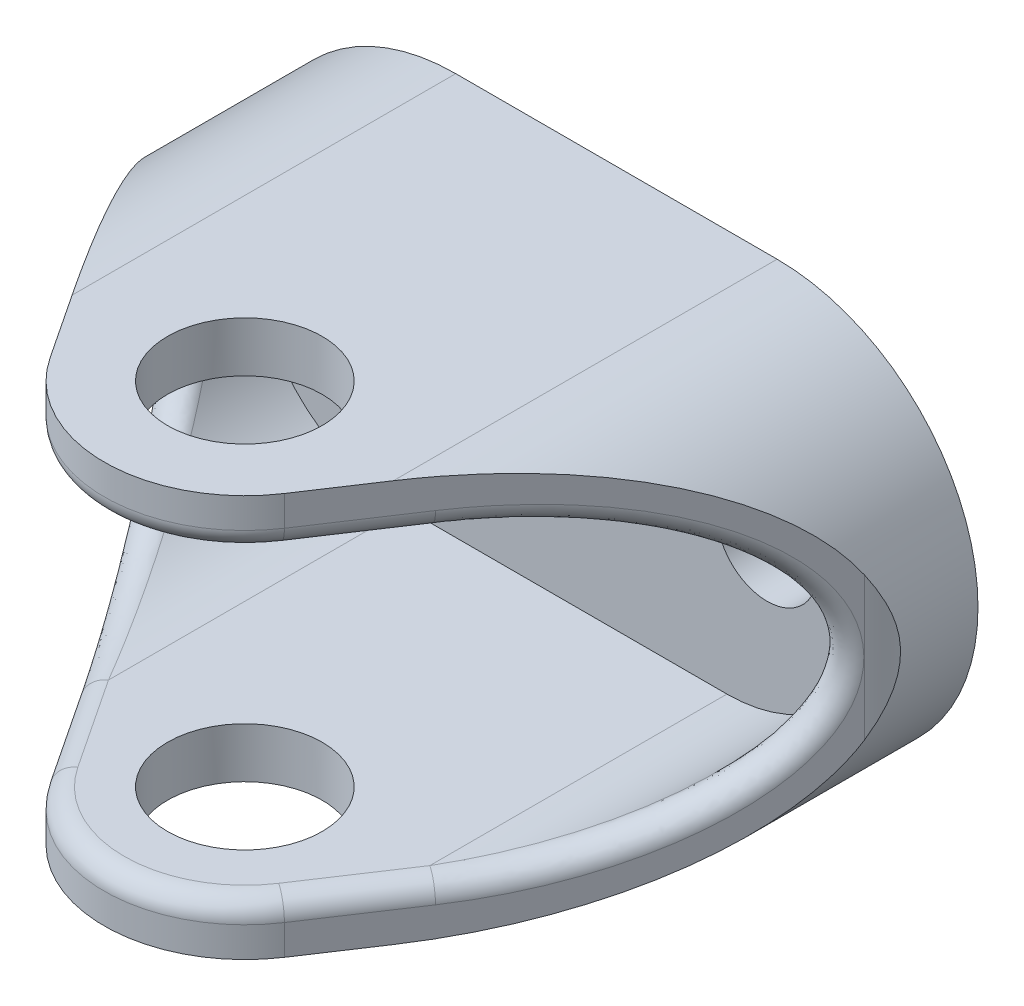
SolidWorks part; units mm, degrees
note: '?' marks a value the reader was unsure of.
material "6061 Alloy"
ref_plane "Front Plane" through (0, 0, 0) normal (0, 0, 1) x (1, 0, 0)
ref_plane "Top Plane" through (0, 0, 0) normal (0, 1, 0) x (1, 0, 0)
ref_plane "Right Plane" through (0, 0, 0) normal (1, 0, 0) x (0, 0, -1)
sketch "Sketch1" plane through (0, 0, 0) normal (0, 1, 0) x (1, 0, 0)
  line L0 (-24.13, -19.05) -> (24.13, -19.05)
  line L1 (-24.13, -19.05) -> (-24.13, 19.05)
  line L2 (24.13, -19.05) -> (24.13, 19.05)
  line L3 (-24.13, 19.05) -> (24.13, 19.05)
  line L4 (-24.13, -19.05) -> (24.13, 19.05) construction
  line L5 (24.13, -19.05) -> (-24.13, 19.05) construction
  point P1 (0, 0)
  dimension "D1" = 38.1
  dimension "D2" = 48.26
extrude "Billet" add sketch "Sketch1" along normal blind 25.4
sketch "Sketch2" plane through (0, 25.4, 0) normal (0, 1, 0) x (1, 0, 0)
  line L1 (-7.4106, -9.3557) -> (-24.13, 15.875)
  line L3 (24.13, 19.05) -> (-24.13, 19.05) construction
  line L4 (-24.13, 15.875) -> (24.13, 15.875) construction
  line L5 (0, -14.605) -> (0, -11.9174) construction
  line L6 (-24.13, 15.875) -> (-24.13, -19.05)
  line L7 (-24.13, -19.05) -> (24.13, -19.05)
  line L8 (24.13, -19.05) -> (24.13, 15.875)
  line L9 (7.4106, -9.3557) -> (24.13, 15.875)
  arc A0 (7.4106, -9.3557) -> (-7.4106, -9.3557) centre (0, -4.445) cw
  circle A1 centre (0, -4.445) radius 4.8895
  dimension "D1" = 8.89
  dimension "D3" = 9.779
  dimension "D2" = 3.175
  dimension "D4" = 20.32
extrude "Mill Cut 1" cut sketch "Sketch2" against normal through all
fillet "Fillet2" radius 12.7 2 edges at (-24.13, 12.7, -15.875) (24.13, 12.7, -15.875)
fillet "Fillet1" [suppressed] radius 1.27
ref_plane "Plane2" through (0, 25.4, 13.335) normal (0, 0, 1) x (1, 0, 0)
sketch "Sketch6" plane through (0, 25.4, 13.335) normal (0, 0, 1) x (1, 0, 0)
  line L0 (7.4106, 0) -> (-7.4106, 0) construction
  line L1 (-10.16, -3.175) -> (10.16, -3.175)
  line L2 (-10.16, -3.175) -> (-10.16, -22.225)
  line L3 (-10.16, -22.225) -> (10.16, -22.225)
  line L4 (10.16, -3.175) -> (10.16, -22.225)
  line L5 (0, -3.175) -> (0, 0) construction
  line L6 (0, -22.225) -> (0, -25.4) construction
  line L7 (-24.13, 0) -> (-24.13, -25.4) construction
  arc A0 (-10.16, -3.175) -> (-10.16, -22.225) centre (-10.16, -12.7) ccw
  arc A1 (10.16, -3.175) -> (10.16, -22.225) centre (10.16, -12.7) cw
  point P6 (0, 0)
  point P7 (0, -3.175)
  dimension "D1" = 3.175
  dimension "D2" = 13.97
extrude "Cut-Extrude1" cut sketch "Sketch6" against normal offset from surface (29.21 mm away) 3.175 up to face at (0, 12.7, -19.05)
sketch "Sketch8" plane through (0, 25.4, 13.335) normal (0, 0, 1) x (1, 0, 0)
  line L7 (-7.4106, 0) -> (-22.0347, 0) construction
  line L8 (-10.16, -25.4) -> (-60.96, -25.4)
  line L9 (-60.96, -25.4) -> (-60.96, 0)
  line L10 (-60.96, 0) -> (-10.16, 0)
  line L11 (-7.4106, -25.4) -> (-22.0347, -25.4) construction
  arc A4 (-10.16, 0) -> (-10.16, -25.4) centre (-10.16, -12.7) ccw
  arc A8 (-10.16, -3.175) -> (-10.16, -22.225) centre (-10.16, -12.7) ccw construction
  dimension "D1" = 50.8
extrude "Cut-Extrude2" cut sketch "Sketch8" against normal through all
mirror "Mirror1" about plane through (0, 0, 0) normal (1, 0, 0) of "Cut-Extrude2"
sketch "Sketch9" plane through (0, 0, -15.875) normal (0, 0, 1) x (1, 0, 0)
  line L0 (0, 25.4) -> (0, 0) construction
  line L1 (7.4106, 25.4) -> (-7.4106, 25.4) construction
  line L2 (0, 12.7) -> (12.7, 12.7) construction
  circle A0 centre (12.7, 12.7) radius 3.175
  circle A1 centre (-12.7, 12.7) radius 3.175
  dimension "D1" = 6.35
  dimension "D2" = 12.7
extrude "Holes" cut sketch "Sketch9" against normal through all
fillet "Fillet3" [suppressed] radius 1.27
fillet "Fillet4" radius 1.27 8 edges at (-8.7853, 3.175, 7.2812) (0, 3.175, 13.335) (8.7853, 3.175, 7.2812) (19.685, 12.7, -9.1672) (8.7853, 22.225, 7.2812) (0, 22.225, 13.335) (-8.7853, 22.225, 7.2812) (-19.685, 12.7, -9.1672)
ref_axis "Axis1" [suppressed] through (0, 22.225, 4.445) along (0, 1, 0)?
ref_plane "Plane1" [suppressed] through (1.4286, 0, 0.52) normal (-0.9397, 0, -0.342) x (0, 1, 0)
sketch "Sketch5" [suppressed] plane through (0, 25.4, 0) normal (0, 1, 0) x (1, 0, 0)
  circle A0 centre (0, -4.445) radius 4.8895
extrude "Mock Bolt" [suppressed] add sketch "Sketch5" against normal through all
